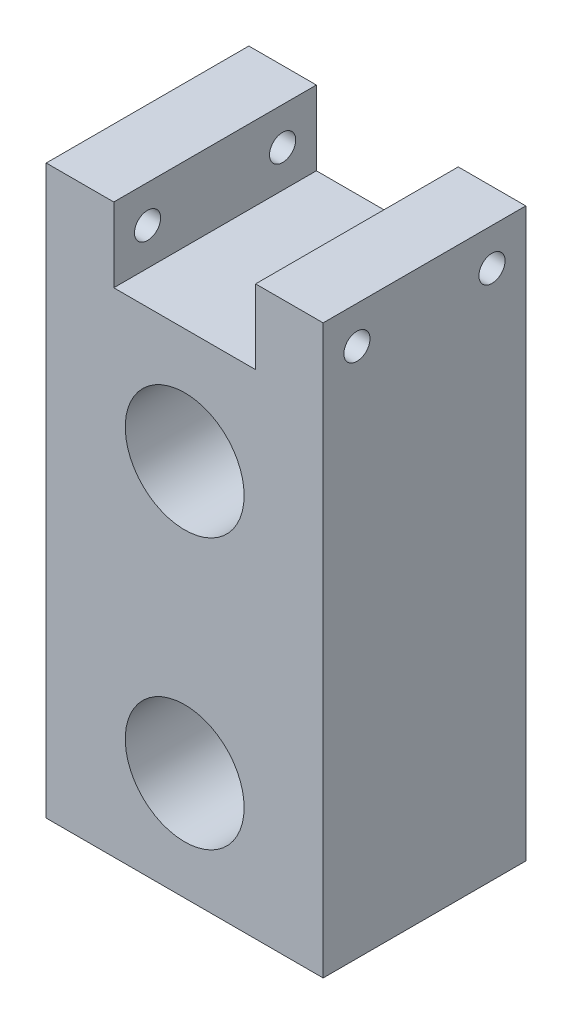
SolidWorks part; units mm, degrees
ref_plane "Front Plane" through (0, 0, 0) normal (0, 0, 1) x (1, 0, 0)
ref_plane "Top Plane" through (0, 0, 0) normal (0, 1, 0) x (1, 0, 0)
ref_plane "Right Plane" through (0, 0, 0) normal (1, 0, 0) x (0, 0, -1)
sketch "Sketch1" plane through (0, 0, 0) normal (0, 0, 1) x (1, 0, 0)
  line L0 (13.335, 21.59) -> (-13.335, 21.59)
  line L1 (-13.335, 21.59) -> (-13.335, 35.56)
  line L2 (-13.335, 35.56) -> (-26.035, 35.56)
  line L3 (-26.035, 35.56) -> (-26.035, -71.12)
  line L4 (-26.035, -71.12) -> (26.035, -71.12)
  line L5 (0, 0) -> (0, 45.5255) construction
  line L6 (26.035, 35.56) -> (26.035, -71.12)
  line L7 (13.335, 35.56) -> (26.035, 35.56)
  line L8 (13.335, 21.59) -> (13.335, 35.56)
  point P7 (0, -71.12)
  point P15 (0, 21.59)
  dimension "D1" = 21.59
  dimension "D2" = 13.97
  dimension "D3" = 12.7
  dimension "D4" = 71.12
  dimension "D5" = 13.335
extrude "Boss-Extrude1" add sketch "Sketch1" along normal mid plane 38.1
sketch "Sketch2" plane through (0, 0, 19.05) normal (0, 0, 1) x (1, 0, 0)
  circle A0 centre (0, 0) radius 11.176
  circle A1 centre (0, -50.8) radius 11.176
  dimension "D1" = 22.352
  dimension "D3" = 22.352
  dimension "D2" = 50.8
extrude "Cut-Extrude1" cut sketch "Sketch2" against normal up to surface (38.1 mm away) up to face at (0, 5.3975, -19.05)
hole_wizard "#10 (0.1935) Diameter Hole1" positions "Sketch5" profile "Sketch6" hole size "#10" standard "ANSI Inch" end condition through all
sketch "Sketch5" plane through (26.035, 0, 0) normal (1, 0, 0) x (0, 0, -1)
  point P0 (-12.7, 28.575)
  dimension "D1" = 12.7
  dimension "D2" = 28.575
sketch "Sketch6" plane through (26.035, 28.575, 12.7) normal (0, 1, 0) x (0, 0, -1)
  line L0 (0, 0) -> (0, 52.07)
  line L1 (0, 52.07) -> (2.4574, 52.07)
  line L2 (2.4574, 52.07) -> (2.4574, 0)
  line L5 (2.4574, 0) -> (0, 0)
  line L11 (0, -6.35) -> (0, 107.95) construction
  dimension "Thru Hole Dia." = 4.9149
  dimension "Thru Hole Depth" = 52.07
mirror "Mirror1" about plane through (0, 0, 0) normal (0, 0, 1) of "#10 (0.1935) Diameter Hole1"
